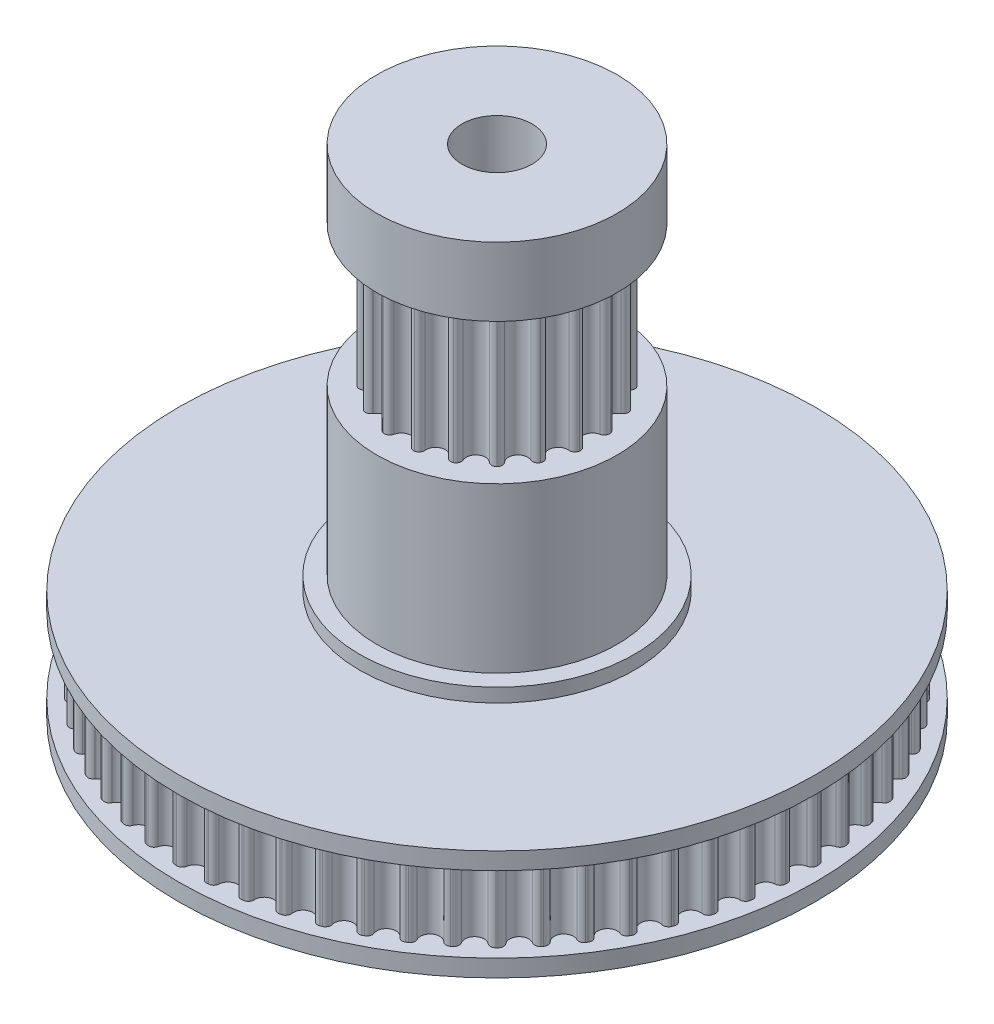
SolidWorks part; units mm, degrees
ref_plane "Front Plane" through (0, 0, 0) normal (0, 0, 1) x (1, 0, 0)
ref_plane "Top Plane" through (0, 0, 0) normal (0, 1, 0) x (1, 0, 0)
ref_plane "Right Plane" through (0, 0, 0) normal (1, 0, 0) x (0, 0, -1)
sketch "PulleyOffsets" plane through (0, 0, 0) normal (1, 0, 0) x (0, 0, -1)
  line L0 (14.0115, 0) -> (-14.0115, 0) construction
  line L1 (14.0115, 28.0231) -> (-14.0115, 28.0231) construction
  line L2 (0, 0) -> (0, 28.0231) construction
  point P7 (0, 0)
  point P8 (14.0115, 28.0231)
  dimension "D1" = 28.0231
ref_axis "Axis1" through (0, 34.9332, 0) along (0, -1, 0)
ref_plane "Big Pulley Plane" through (0, 0, 0) normal (0, 1, 0) x (1, 0, 0)
ref_plane "Small Pulley Plane" through (0, 28.0231, 0) normal (0, 1, 0) x (1, 0, 0)
sketch "Sketch1" plane through (0, 0, 0) normal (0, 1, 0) x (1, 0, 0)
  line L0 (0, 0) -> (0, 28.2667) construction
  line L1 (0, 0) -> (2.9202, 27.7837) construction
  circle A0 centre (0, 0) radius 28.2667 construction
  circle A1 centre (0, 0) radius 27.0467 construction
  circle A2 centre (0, 27.9367) radius 0.89 construction
  circle A5 centre (2.9202, 27.7837) radius 0.89 construction
  arc A6 (0, 27.0467) -> (0.8804, 27.8061) centre (0, 27.9367) ccw
  arc A7 (0.8804, 27.8061) -> (1.3997, 28.2321) centre (1.3749, 27.7327) cw
  arc A8 (1.559, 28.2237) -> (2.031, 27.7458) centre (1.5314, 27.7245) cw
  arc A9 (2.8272, 26.8986) -> (2.031, 27.7458) centre (2.9202, 27.7837) cw
  arc A10 (1.3997, 28.2321) -> (1.559, 28.2237) centre (0, 0) cw
  arc A11 (0, 27.0467) -> (2.8272, 26.8986) centre (0, 0) ccw
  dimension "D1" = 56.5335
  dimension "D3" = 1.78
  dimension "D4" = 0.5
  dimension "D2" = 1.22
  dimension "D5" = 6
extrude "Boss-Extrude1" add sketch "Sketch1" along normal mid plane 7.112 contours A6 A11 A9 A8 A7 region at (0.001, 0, -0.0192)
pattern_circular "CirPattern1" count 60 over 360 about axis through (0, 34.9332, 0) along (0, -1, 0) of "Boss-Extrude1"
sketch "Sketch2" plane through (0, 0, 0) normal (1, 0, 0) x (0, 0, -1)
  line L10 (0, 3.5) -> (29.4415, 3.5) construction
  line L11 (0, 3.5) -> (0, 5.0875) construction
  line L12 (0, 5.0875) -> (29.4415, 5.0875) construction
  line L15 (29.4415, 3.5) -> (29.4415, 5.0875) construction
  line L20 (0, 34.9332) -> (0, -6.9932) construction
  line L22 (29.4415, 5.0875) -> (0, 5.0875)
  line L23 (29.4415, 5.0875) -> (29.4415, 3.5)
  line L24 (29.4415, 3.5) -> (0, 3.5)
  line L25 (0, 5.0875) -> (0, 3.5)
  dimension "D1" = 1.5875
  dimension "D2" = 29.4415
  dimension "D3" = 3.5
revolve "Revolve3" add sketch "Sketch2" angle 360 about axis through (0, 34.9332, 0) along (0, -1, 0) region at (0, 4.2937, -14.7207)
mirror "Mirror1" about plane through (0, 0, 0) normal (0, 1, 0) of "Revolve3"
sketch "Sketch3" plane through (0, 0, 0) normal (0, 1, 0) x (1, 0, 0)
  circle A0 centre (0, 0) radius 22.225
  dimension "D1" = 44.45
extrude "Cut-Extrude1" [suppressed] cut sketch "Sketch3" against normal through all both and the other way through all
sketch "Sketch6" plane through (0, 0, 0) normal (0, 1, 0) x (1, 0, 0)
  line L0 (0, 0) -> (0, 9.1676) construction
  line L1 (0, 0) -> (2.731, 8.405) construction
  circle A0 centre (0, 0) radius 9.1676 construction
  circle A1 centre (0, 0) radius 7.9476 construction
  circle A2 centre (0, 8.8376) radius 0.89 construction
  circle A5 centre (2.731, 8.405) radius 0.89 construction
  arc A6 (0, 7.9476) -> (0.8721, 8.6598) centre (0, 8.8376) ccw
  arc A7 (0.8721, 8.6598) -> (1.4405, 9.0537) centre (1.362, 8.5599) cw
  arc A8 (1.4277, 9.0557) -> (1.8466, 8.5054) centre (1.3498, 8.5618) cw
  arc A9 (2.4559, 7.5586) -> (1.8466, 8.5054) centre (2.731, 8.405) cw
  arc A10 (1.4405, 9.0537) -> (1.4277, 9.0557) centre (0, 0) cw construction
  arc A11 (0, 7.9476) -> (2.4559, 7.5586) centre (0, 0) ccw
  arc A12 (1.4405, 9.0537) -> (1.4277, 9.0557) centre (0, 0) cw
  dimension "D3" = 1.78
  dimension "D4" = 0.5
  dimension "D2" = 1.22
  dimension "D1" = 18.3352
  dimension "D5" = 18
extrude "Boss-Extrude2" add sketch "Sketch6" along normal mid plane 13 from surface contours A6 A11 A9 A8 A7 region at (0.0089, 0, -0.0564) starting at plane "Small Pulley Plane"
pattern_circular "CirPattern2" count 20 over 360 about axis through (0, 34.9332, 0) along (0, -1, 0) of "Boss-Extrude2"
sketch "Sketch4" plane through (0, 0, 0) normal (0, 0, 1) x (1, 0, 0)
  line L0 (12.7, 5.0875) -> (-12.7, 5.0875) construction
  line L1 (29.4415, 5.0875) -> (-29.4415, 5.0875) construction
  line L2 (-12.7, 5.0875) -> (-12.7, 6.3575)
  line L3 (-12.7, 6.3575) -> (-11.1125, 6.3575)
  line L4 (-11.1125, 6.3575) -> (-11.1125, 21.5231)
  line L5 (0, 0) -> (0, 40.8731) construction
  line L6 (11.1125, 6.3575) -> (11.1125, 21.5231) construction
  line L7 (12.7, 6.3575) -> (11.1125, 6.3575) construction
  line L8 (12.7, 5.0875) -> (12.7, 6.3575) construction
  line L9 (-11.1125, 21.5231) -> (11.1125, 21.5231) construction
  line L10 (-12.7, 5.0875) -> (0, 5.0875)
  line L11 (0, 5.0875) -> (0, 21.5231)
  line L12 (0, 21.5231) -> (-11.1125, 21.5231)
  line L13 (1.841, 21.5231) -> (3.5054, 21.5231) construction
  line L14 (0.8721, 34.5231) -> (-0.8721, 34.5231) construction
  line L15 (-11.1125, 40.8731) -> (0, 40.8731)
  line L16 (-11.1125, 40.8731) -> (-11.1125, 34.5231)
  line L17 (-11.1125, 34.5231) -> (0, 34.5231)
  line L18 (0, 40.8731) -> (0, 34.5231)
  line L19 (-11.1125, 21.5231) -> (-11.1125, 34.5231) construction
  point P14 (0, 5.0875)
  dimension "D1" = 1.27
  dimension "D2" = 25.4
  dimension "D3" = 22.225
  dimension "D4" = 6.35
revolve "Revolve4" add sketch "Sketch4" angle 360 about L11
sketch "Sketch7" plane through (0, 40.8731, 0) normal (0, 1, 0) x (1, 0, 0)
  circle A0 centre (0, 0) radius 3.2385
  dimension "D1" = 6.477
extrude "Cut-Extrude2" cut sketch "Sketch7" against normal through all both and the other way through all
sketch "Sketch8" plane through (0, -5.0875, 0) normal (0, -1, 0) x (1, 0, 0)
  circle A0 centre (0, 0) radius 4.7625
  dimension "D1" = 9.525
equation "\"TEETH_NUM\"= 60"
equation "\"TOOTH_PITCH\"= 3mm"
equation "\"PITCH_LINE_OFFSET\"= .015in"
equation "\"DIAMETER_PER_GROOVE\"= \"OUTSIDE_DIAMETER\" / \"TEETH_NUM\" * 1in"
equation "\"PITCH_DIAMETER\"= ( ( \"TEETH_NUM\" * 3 - 1.31 ) / 3.1415 + .415 ) * 1mm"
equation "\"OUTSIDE_DIAMETER\"= \"PITCH_DIAMETER\" - \"PITCH_LINE_OFFSET\" * 2"
equation "\"D1@Sketch1\"=\"OUTSIDE_DIAMETER\""
equation "\"TOOTH_HEIGHT\"= 1.22mm"
equation "\"D2@Sketch1\"=\"TOOTH_HEIGHT\""
equation "\"TOOTH_DIAMETER\"= 1.78mm"
equation "\"INTERNAL_RADIUS\"= .5mm"
equation "\"D3@Sketch1\"=\"TOOTH_DIAMETER\""
equation "\"D5@Sketch1\"=360 / \"TEETH_NUM\""
equation "\"D4@Sketch1\"=\"INTERNAL_RADIUS\""
equation "\"D1@CirPattern1\"=\"TEETH_NUM\""
equation "\"BELT_GAP\"= 7mm"
equation "\"D2@Sketch2\"=\"PITCH_DIAMETER\"/2+1/32"
equation "\"D3@Sketch2\"=\"BELT_GAP\"/2"
equation "\"2_TEETH_NUM\"= 20"
equation "\"2_PITCH_DIAMETER\"= ( ( \"2_TEETH_NUM\" * 3 - 1.31 ) / 3.1415 + .415 ) * 1mm"
equation "\"2_OUTSIDE_DIAMETER\"= \"2_PITCH_DIAMETER\" - \"PITCH_LINE_OFFSET\" * 2"
equation "\"2_DIAMETER_PER_GROOVE\"= \"2_OUTSIDE_DIAMETER\" / \"2_TEETH_NUM\" * 1in"
equation "\"D5@Sketch6\"=360/\"2_TEETH_NUM\""
equation "\"D1@Sketch6\"=\"2_OUTSIDE_DIAMETER\""
equation "\"D2@Sketch6\"=\"TOOTH_HEIGHT\""
equation "\"D3@Sketch6\"=\"TOOTH_DIAMETER\""
equation "\"D4@Sketch6\"=\"INTERNAL_RADIUS\""
equation "\"2_BELT_GAP\"= 13mm"
equation "\"D1@CirPattern2\"=\"2_TEETH_NUM\""
equation "\"D1@Boss-Extrude2\"=\"2_BELT_GAP\""
equation "\"Pulley_OffSets\"=1.10327"
equation "\"D1@PulleyOffsets\" = \"Pulley_OffSets\""
